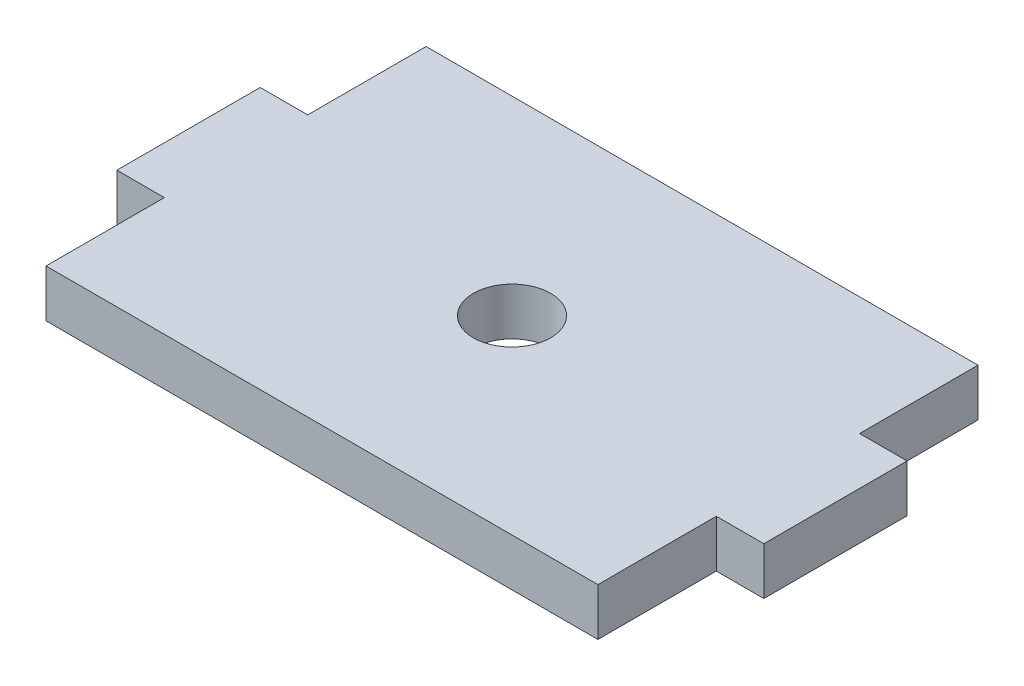
SolidWorks part; units mm, degrees
ref_plane "Front Plane" through (0, 0, 0) normal (0, 0, 1) x (1, 0, 0)
ref_plane "Top Plane" through (0, 0, 0) normal (0, 1, 0) x (1, 0, 0)
ref_plane "Right Plane" through (0, 0, 0) normal (1, 0, 0) x (0, 0, -1)
sketch "Sketch1" plane through (0, 0, 0) normal (0, 1, 0) x (1, 0, 0)
  line L0 (-18.4404, -4.7879) -> (-18.4404, -12.7)
  line L1 (-18.4404, 12.7) -> (18.4404, 12.7)
  line L2 (-18.4404, 12.7) -> (-18.4404, 4.7879)
  line L3 (-18.4404, -12.7) -> (18.4404, -12.7)
  line L4 (18.4404, 12.7) -> (18.4404, 4.7879)
  line L5 (-18.4404, 12.7) -> (18.4404, -12.7) construction
  line L6 (-18.4404, -12.7) -> (18.4404, 12.7) construction
  line L7 (18.4404, 4.7879) -> (21.6154, 4.7879)
  line L9 (18.4404, -4.7879) -> (21.6154, -4.7879)
  line L10 (21.6154, 4.7879) -> (21.6154, -4.7879)
  line L11 (-21.6154, 0) -> (21.6154, 0) construction
  line L13 (-21.6154, 4.7879) -> (-18.4404, 4.7879)
  line L14 (-21.6154, 4.7879) -> (-21.6154, -4.7879)
  line L15 (-21.6154, -4.7879) -> (-18.4404, -4.7879)
  line L19 (18.4404, -4.7879) -> (18.4404, -12.7)
  circle A0 centre (0, 0) radius 2.5797
  point P0 (0, 0)
  dimension "D6" = 5.1594
  dimension "D1" = 25.4
  dimension "D2" = 3.175
  dimension "D3" = 9.5758
  dimension "D4" = 36.8808
  dimension "D5" = 3.175
extrude "Boss-Extrude1" add sketch "Sketch1" along normal mid plane 3.175 contours L19 L9 L10 L7 L4 L1 L2 L13 L14 L15 L0 L3 A0 region at (-20.0279, 0, 4.2865)
equation "\"D3@Sketch1\"=0.375in+0.002in"
equation "\"D4@Sketch1\"=2.00in-.375-.173"
